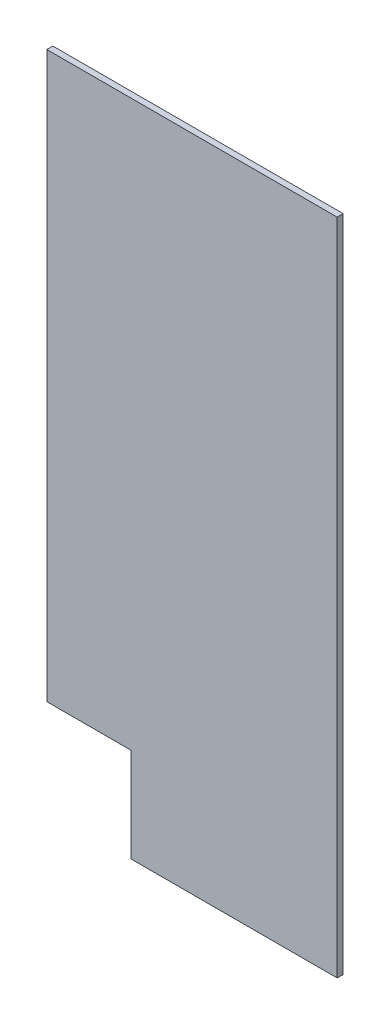
SolidWorks part; units mm, degrees
ref_plane "Plan de face" through (0, 0, 0) normal (0, 0, 1) x (1, 0, 0)
ref_plane "Plan de dessus" through (0, 0, 0) normal (0, 1, 0) x (1, 0, 0)
ref_plane "Plan de droite" through (0, 0, 0) normal (1, 0, 0) x (0, 0, -1)
sketch "Esquisse1" plane through (0, 0, 0) normal (0, 0, 1) x (1, 0, 0)
  line L1 (-37.547, 269.1613) -> (117.453, 269.1613)
  line L2 (-37.547, 269.1613) -> (-37.547, -59.8387)
  line L3 (-37.547, -59.8387) -> (117.453, -59.8387)
  line L4 (117.453, 269.1613) -> (117.453, -59.8387)
  dimension "D1" = 329
  dimension "D2" = 155
extrude "Boss.-Extru.1" add sketch "Esquisse1" along normal blind 3
sketch "Esquisse2" plane through (0, 0, 3) normal (0, 0, 1) x (1, 0, 0)
  line L0 (-27.547, -12.8387) -> (-27.547, 269.1613)
  line L1 (14.453, -12.8387) -> (-27.547, -12.8387)
  line L2 (14.453, -12.8387) -> (14.453, -59.8387)
  line L3 (14.453, -59.8387) -> (-37.547, -59.8387)
  line L4 (-37.547, -12.8387) -> (-37.547, -59.8387)
  line L5 (117.453, 269.1613) -> (-37.547, 269.1613) construction
  line L6 (-27.547, 269.1613) -> (-37.547, 269.1613)
  line L7 (-37.547, 269.1613) -> (-37.547, -12.8387)
  dimension "D1" = 52
  dimension "D2" = 47
  dimension "D3" = 10
extrude "Enlèv. mat.-Extru.1" cut sketch "Esquisse2" against normal blind 10
